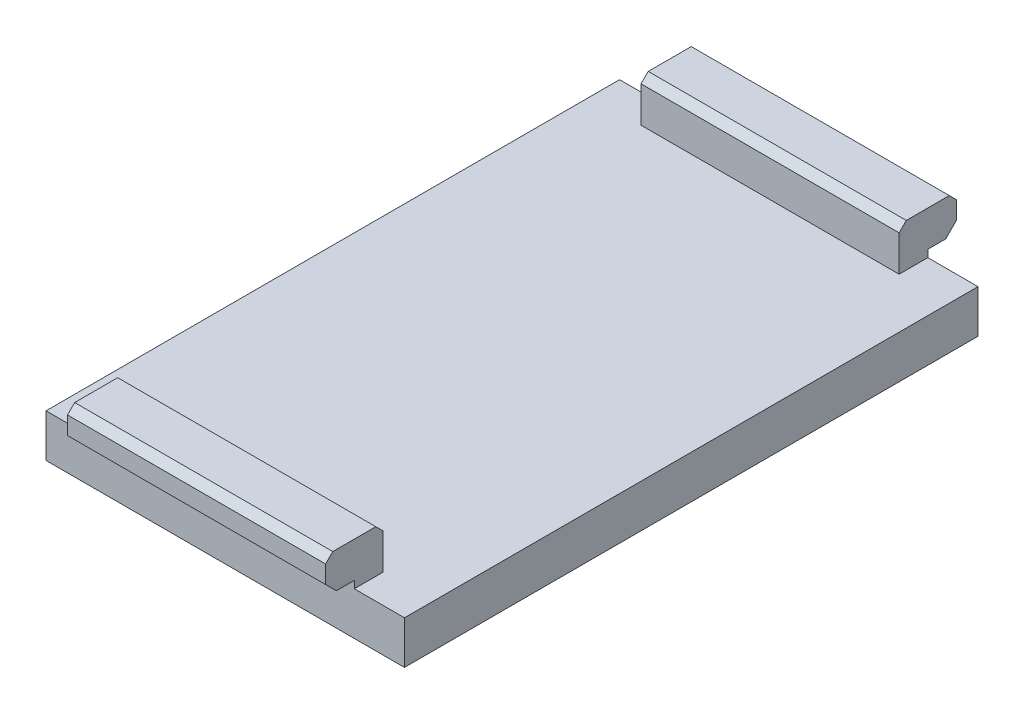
SolidWorks part; units mm, degrees
ref_plane "Front" through (0, 0, 0) normal (0, 0, 1) x (1, 0, 0)
ref_plane "Top" through (0, 0, 0) normal (0, 1, 0) x (1, 0, 0)
ref_plane "Right" through (0, 0, 0) normal (1, 0, 0) x (0, 0, -1)
sketch "Эскиз1" plane through (0, 0, 0) normal (0, 0, 1) x (1, 0, 0)
  line L1 (-17.0795, 18.39) -> (7.9205, 18.39)
  line L2 (-17.0795, 18.39) -> (-17.0795, 15.39)
  line L3 (-17.0795, 15.39) -> (7.9205, 15.39)
  line L4 (7.9205, 18.39) -> (7.9205, 15.39)
  dimension "D1" = 3
  dimension "D2" = 25
extrude "Бобышка-Вытянуть1" add sketch "Эскиз1" along normal blind 20
sketch "Эскиз2" plane through (0, 18.39, 0) normal (0, 1, 0) x (1, 0, 0)
  line L0 (7.9205, 0) -> (-17.0795, 0) construction
  line L1 (-13.5795, 0) -> (4.4205, 0)
  line L2 (-13.5795, 0) -> (-13.5795, -2)
  line L3 (-13.5795, -2) -> (4.4205, -2)
  line L4 (4.4205, 0) -> (4.4205, -2)
  line L5 (7.9205, -20) -> (7.9205, 0) construction
  line L6 (-17.0795, -20) -> (-17.0795, 0) construction
  dimension "D1" = 3.5
  dimension "D2" = 3.5
  dimension "D3" = 2
extrude "Бобышка-Вытянуть2" add sketch "Эскиз2" along normal blind 3
sketch "Эскиз3" plane through (0, 0, 0) normal (0, 0, -1) x (-1, 0, 0)
  line L0 (13.5795, 21.39) -> (13.5795, 18.39) construction
  line L1 (-4.4205, 21.39) -> (13.5795, 21.39)
  line L2 (-4.4205, 21.39) -> (-4.4205, 19.89)
  line L4 (13.5795, 21.39) -> (13.5795, 19.89)
  line L5 (-4.4205, 19.89) -> (-4.4205, 18.8965)
  line L6 (-4.4205, 21.39) -> (-4.4205, 18.39) construction
  line L7 (-4.4205, 18.8965) -> (13.5795, 18.8965)
  line L8 (13.5795, 18.8965) -> (13.5795, 19.89)
extrude "Бобышка-Вытянуть3" add sketch "Эскиз3" along normal blind 2
chamfer "Фаска1" distance 0.75 angle 45 1 edges at (-4.5795, 18.8965, -2)
chamfer "Фаска2" distance 0.5 angle 45 1 edges at (-4.5795, 21.39, -2)
chamfer "Фаска3" distance 0.5 angle 45 1 edges at (-4.5795, 21.39, 2)
mirror "Зеркальное отражение1" about plane through (0, 0, 20) normal (0, 0, 1) of bodies 103
